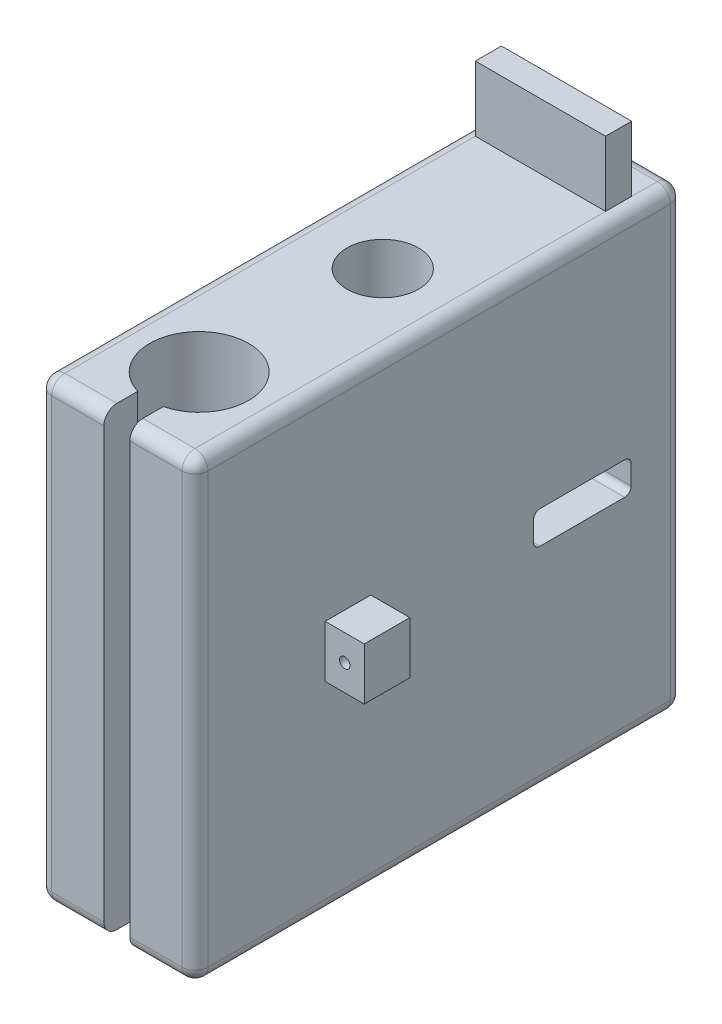
SolidWorks part; units mm, degrees
ref_plane "Front Plane" through (0, 0, 0) normal (0, 0, 1) x (1, 0, 0)
ref_plane "Top Plane" through (0, 0, 0) normal (0, 1, 0) x (1, 0, 0)
ref_plane "Right Plane" through (0, 0, 0) normal (1, 0, 0) x (0, 0, -1)
ref_plane "Plano1" through (-220, 0, 0) normal (1, 0, 0) x (0, 0, -1)
sketch "Esboço1" plane through (-220, 0, 0) normal (1, 0, 0) x (0, 0, -1)
  line L0 (-460.4999, 246.154) -> (-460.4999, 230.354) construction
  line L1 (-465.4999, 248.254) -> (-390.4999, 248.254)
  line L2 (-465.4999, 248.254) -> (-465.4999, 178.254)
  line L3 (-465.4999, 178.254) -> (-390.4999, 178.254)
  line L4 (-390.4999, 248.254) -> (-390.4999, 178.254)
  dimension "D1" = 75
  dimension "D2" = 70
  dimension "D3" = 5
extrude "Ressalto-extrusão1" add sketch "Esboço1" along normal blind 12 and the other way blind 12
sketch "Esboço3" plane through (0, 248.254, 0) normal (0, 1, 0) x (1, 0, 0)
  line L5 (-232, -465.4999) -> (-208, -465.4999) construction
  line L7 (-220, -465.4999) -> (-218, -465.4999)
  line L10 (-218, -465.4999) -> (-218, -460.3692)
  line L11 (-220, -465.4999) -> (-222, -465.4999)
  line L14 (-222, -465.4999) -> (-222, -460.292)
  arc A3 (-218, -460.3692) -> (-222, -460.292) centre (-219.8586, -452.9999) ccw
  circle A8 centre (-219.5085, -425.1499) radius 5.5
  circle A9 centre (-219.5085, -425.1499) radius 5.5
  dimension "D1" = 15.2
  dimension "D3" = 2
  dimension "D4" = 2
  dimension "D2" = 0.5
extrude "Corte-extrusão1" cut sketch "Esboço3" against normal through all
sketch "Esboço4" plane through (0, 0, 390.4999) normal (0, 0, -1) x (-1, 0, 0)
  line L0 (220, 248.254) -> (220, 178.254) construction
  line L1 (232, 248.254) -> (208, 248.254) construction
  line L2 (232, 178.254) -> (208, 178.254) construction
  circle A0 centre (219.8586, 238.254) radius 4.1
  circle A1 centre (219.8586, 188.254) radius 4.1
  dimension "D1" = 8.2
  dimension "D2" = 8.2
extrude "Corte-extrusão2" cut sketch "Esboço4" against normal blind 20
fillet "Filete1" radius 2 14 edges at (-227, 178.254, 465.4999) (-213, 178.254, 465.4999) (-213, 248.254, 465.4999) (-227, 248.254, 465.4999) (-208, 178.254, 427.9999) (-208, 248.254, 427.9999) (-208, 213.254, 465.4999) (-232, 178.254, 427.9999) (-232, 213.254, 465.4999) (-232, 248.254, 427.9999) (-220, 248.254, 390.4999) (-220, 178.254, 390.4999) (-208, 213.254, 390.4999) (-232, 213.254, 390.4999)
sketch "Esboço5" plane through (0, 0, 390.4999) normal (0, 0, -1) x (-1, 0, 0)
  line L8 (213.9582, 195.2587) -> (225.9582, 195.2489)
  line L9 (225.9582, 195.2489) -> (225.9877, 231.2489)
  line L10 (225.9877, 231.2489) -> (213.9877, 231.2587)
  line L11 (213.9877, 231.2587) -> (213.9582, 195.2587)
  line L12 (213.9582, 195.2587) -> (225.9582, 195.2489)
  line L13 (225.9582, 195.2489) -> (225.9877, 231.2489)
  line L14 (225.9877, 231.2489) -> (213.9877, 231.2587)
  line L15 (213.9877, 231.2587) -> (213.9582, 195.2587)
  dimension "D1" = 0
extrude "Corte-extrusão3" cut sketch "Esboço5" against normal blind 29
sketch "Esboço6" plane through (-232, 0, 0) normal (-1, 0, 0) x (0, 0, 1)
  line L0 (392.4999, 213.254) -> (463.4999, 213.254) construction
  line L1 (392.4999, 246.254) -> (392.4999, 180.254) construction
  line L2 (463.4999, 180.254) -> (463.4999, 246.254) construction
  line L3 (398.4999, 213.254) -> (413.4999, 213.254) construction
  line L4 (399.4999, 215.754) -> (412.4999, 215.754)
  line L5 (398.4999, 214.754) -> (398.4999, 211.754)
  line L6 (399.4999, 210.754) -> (412.4999, 210.754)
  line L7 (413.4999, 214.754) -> (413.4999, 211.754)
  arc A0 (412.4999, 215.754) -> (413.4999, 214.754) centre (412.4999, 214.754) cw
  arc A1 (412.4999, 210.754) -> (413.4999, 211.754) centre (412.4999, 211.754) ccw
  arc A2 (398.4999, 211.754) -> (399.4999, 210.754) centre (399.4999, 211.754) ccw
  arc A3 (399.4999, 215.754) -> (398.4999, 214.754) centre (399.4999, 214.754) ccw
  point P14 (413.4999, 215.754)
  point P17 (413.4999, 210.754)
  point P22 (398.4999, 215.754)
  dimension "D4" = 1
  dimension "D1" = 5
  dimension "D2" = 15
  dimension "D3" = 6
extrude "Corte-extrusão4" cut sketch "Esboço6" against normal blind 28
sketch "Esboço7" plane through (-208, 0, 0) normal (1, 0, 0) x (0, 0, -1)
  line L0 (-463.4999, 246.254) -> (-463.4999, 180.254) construction
  line L1 (-445.4999, 217.254) -> (-438.4999, 217.254)
  line L2 (-445.4999, 217.254) -> (-445.4999, 209.254)
  line L3 (-445.4999, 209.254) -> (-438.4999, 209.254)
  line L4 (-438.4999, 217.254) -> (-438.4999, 209.254)
  line L5 (-465.4999, 180.254) -> (-465.4999, 246.254) construction
  point P6 (-463.4999, 213.254)
  point P7 (-445.4999, 213.254)
  dimension "D1" = 7
  dimension "D2" = 8
  dimension "D3" = 20
extrude "Ressalto-extrusão2" add sketch "Esboço7" along normal blind 6 and the other way blind 30
ref_point "Ponto1"
sketch "Esboço9" plane through (0, 0, 445.4999) normal (0, 0, 1) x (1, 0, 0)
  line L0 (-205, 217.254) -> (-205, 209.254) construction
  line L3 (-208, 217.254) -> (-202, 217.254) construction
  line L6 (-208, 209.254) -> (-202, 209.254) construction
  line L7 (-208, 213.254) -> (-202, 213.254) construction
  line L8 (-208, 246.254) -> (-208, 180.254) construction
  line L9 (-202, 217.254) -> (-202, 209.254) construction
hole_wizard "Broca de rosquear para tarraxa de M2x0.41" positions "Esboço13" profile "Esboço14" hole size "M2x0.4" standard "Ansi Metric" end condition through all
sketch "Esboço13" plane through (0, 0, 445.4999) normal (0, 0, 1) x (1, 0, 0)
  line L0 (-205, 217.254) -> (-205, 209.254) construction
  point P0 (-205, 213.254)
sketch "Esboço14" plane through (-205, 213.254, 445.4999) normal (1, 0, 0) x (0, -1, 0)
  line L0 (0, 0) -> (0, 55)
  line L1 (0, 55) -> (0.8, 55)
  line L2 (0.8, 55) -> (0.8, 0)
  line L5 (0.8, 0) -> (0, 0)
  line L11 (0, -6.35) -> (0, 107.95) construction
  dimension "Thru Hole Dia." = 1.6
  dimension "Thru Hole Depth" = 55
sketch "Esboço15" plane through (0, 0, 445.4999) normal (0, 0, 1) x (1, 0, 0)
  line L0 (-235, 217.254) -> (-235, 209.254) construction
  line L1 (-238, 217.254) -> (-232, 217.254) construction
  line L2 (-238, 209.254) -> (-232, 209.254) construction
  line L3 (-238, 213.254) -> (-232, 213.254) construction
  line L4 (-238, 217.254) -> (-238, 209.254) construction
  line L5 (-232, 180.254) -> (-232, 246.254) construction
hole_wizard "Broca de rosquear para tarraxa de M2x0.42" positions "Esboço16" profile "Esboço17" hole size "M2x0.4" standard "Ansi Metric" end condition through all
sketch "Esboço16" plane through (0, 0, 445.4999) normal (0, 0, 1) x (1, 0, 0)
  line L0 (-235, 217.254) -> (-235, 209.254) construction
  point P0 (-235, 213.254)
sketch "Esboço17" plane through (-235, 213.254, 445.4999) normal (1, 0, 0) x (0, -1, 0)
  line L0 (0, 0) -> (0, 55)
  line L1 (0, 55) -> (0.8, 55)
  line L2 (0.8, 55) -> (0.8, 0)
  line L5 (0.8, 0) -> (0, 0)
  line L11 (0, -6.35) -> (0, 107.95) construction
  dimension "Thru Hole Dia." = 1.6
  dimension "Thru Hole Depth" = 55
sketch "Esboço18" plane through (0, 248.254, 0) normal (0, 1, 0) x (1, 0, 0)
  line L0 (-230, -392.4999) -> (-230, -463.4999) construction
  line L1 (-230, -396.4346) -> (-210, -396.4346)
  line L2 (-230, -396.4346) -> (-230, -400.4346)
  line L3 (-230, -400.4346) -> (-210, -400.4346)
  line L4 (-210, -396.4346) -> (-210, -400.4346)
  line L5 (-210, -463.4999) -> (-210, -392.4999) construction
  dimension "D1" = 4
extrude "Ressalto-extrusão3" add sketch "Esboço18" along normal blind 10
